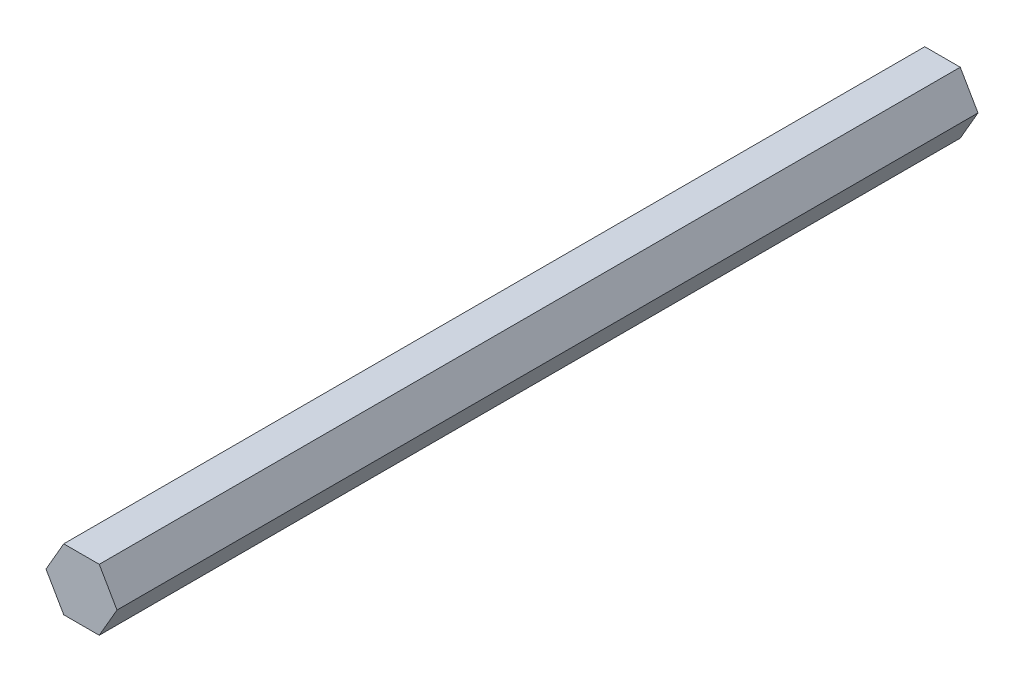
SolidWorks part; units mm, degrees
note: '?' marks a value the reader was unsure of.
ref_plane "Front Plane" through (0, 0, 0) normal (0, 0, 1) x (1, 0, 0)
ref_plane "Top Plane" through (0, 0, 0) normal (0, 1, 0) x (1, 0, 0)
ref_plane "Right Plane" through (0, 0, 0) normal (1, 0, 0) x (0, 0, -1)
sketch "Sketch1" plane through (0, 0, 0) normal (0, 0, 1) x (1, 0, 0)
  line L1 (3.6662, 6.35) -> (-3.6662, 6.35)
  line L2 (-3.6662, 6.35) -> (-7.3323, 0)
  line L3 (-7.3323, 0) -> (-3.6662, -6.35)
  line L4 (-3.6662, -6.35) -> (3.6662, -6.35)
  line L5 (3.6662, -6.35) -> (7.3323, 0)
  line L6 (7.3323, 0) -> (3.6662, 6.35)
  circle A0 centre (0, 0) radius 6.35 construction
  dimension "D1" = 12.7
extrude "Boss-Extrude1" add sketch "Sketch1" along normal mid plane 177.8635
ref_axis "Axis1" through (0, 0, -83.82) along (0, 0, 1)?
